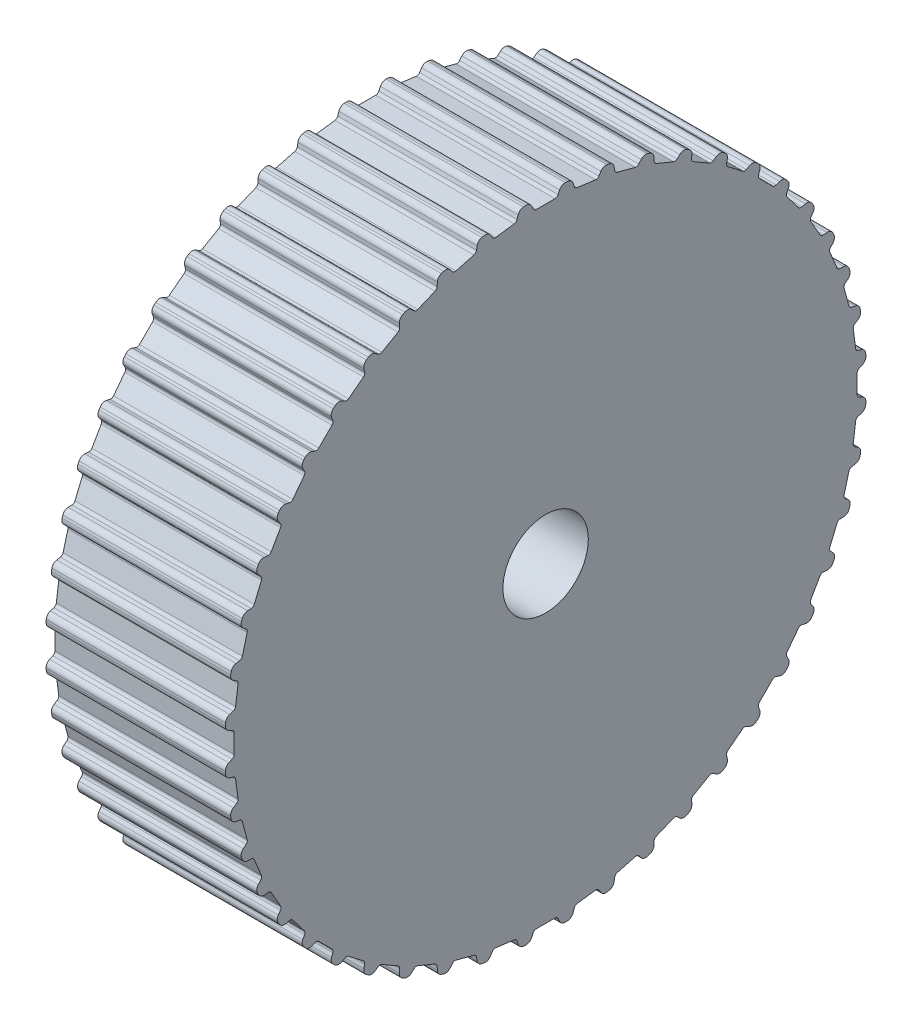
SolidWorks part; units mm, degrees
ref_plane "Front Plane" through (0, 0, 0) normal (0, 0, 1) x (1, 0, 0)
ref_plane "Top Plane" through (0, 0, 0) normal (0, 1, 0) x (1, 0, 0)
ref_plane "Right Plane" through (0, 0, 0) normal (1, 0, 0) x (0, 0, -1)
ref_plane "Plane1" through (0, 0, 0) normal (0, 0, -1) x (-1, 0, 0)
sketch "Sketch1" plane through (0, 0, 0) normal (0, 0, -1) x (-1, 0, 0)
  line L0 (-21, 37.585) -> (-21, 0)
  line L1 (-21, 0) -> (0, 0)
  line L2 (0, 0) -> (0, 37.585)
  line L3 (0, 37.585) -> (-21, 37.585)
  line L4 (-21, 0) -> (0, 0) construction
revolve "Revolve1" add sketch "Sketch1" angle 360 about L4 reverse direction yes
sketch "Sketch2" plane through (0, 0, 0) normal (-1, 0, 0) x (0, 0, 1)
  line L0 (3.0738, 37.4591) -> (3.4238, 36.3491)
  line L1 (3.4238, 36.3491) -> (6.1007, 35.9967)
  line L2 (6.1007, 35.9967) -> (6.7261, 36.9783)
  arc A0 (6.7261, 36.9783) -> (3.0738, 37.4591) centre (0, 0) ccw
extrude "Cut-Extrude1" cut sketch "Sketch2" against normal through all
sketch "Sketch3" plane through (0, 0, 0) normal (-1, 0, 0) x (0, 0, 1)
  line L0 (7.9369, 36.7374) -> (8.139, 35.5912)
  line L1 (8.139, 35.5912) -> (10.747, 34.8924)
  line L2 (10.747, 34.8924) -> (11.4951, 35.784)
  arc A0 (11.4951, 35.784) -> (7.9369, 36.7374) centre (0, 0) ccw
extrude "Cut-Extrude2" cut sketch "Sketch3" against normal through all
sketch "Sketch4" plane through (0, 0, 0) normal (-1, 0, 0) x (0, 0, 1)
  line L0 (12.6642, 35.3871) -> (12.715, 34.2244)
  line L1 (12.715, 34.2244) -> (15.2094, 33.1911)
  line L2 (15.2094, 33.1911) -> (16.0676, 33.9774)
  arc A0 (16.0676, 33.9774) -> (12.6642, 35.3871) centre (0, 0) ccw
extrude "Cut-Extrude3" cut sketch "Sketch4" against normal through all
sketch "Sketch5" plane through (0, 0, 0) normal (-1, 0, 0) x (0, 0, 1)
  line L0 (17.1748, 33.4314) -> (17.0734, 32.2719)
  line L1 (17.0734, 32.2719) -> (19.4116, 30.9219)
  line L2 (19.4116, 30.9219) -> (20.365, 31.5895)
  arc A0 (20.365, 31.5895) -> (17.1748, 33.4314) centre (0, 0) ccw
extrude "Cut-Extrude4" cut sketch "Sketch5" against normal through all
sketch "Sketch6" plane through (0, 0, 0) normal (-1, 0, 0) x (0, 0, 1)
  line L0 (21.3915, 30.9036) -> (21.1396, 29.7673)
  line L1 (21.1396, 29.7673) -> (23.2817, 28.1237)
  line L2 (23.2817, 28.1237) -> (24.3141, 28.6611)
  arc A0 (24.3141, 28.6611) -> (21.3915, 30.9036) centre (0, 0) ccw
extrude "Cut-Extrude5" cut sketch "Sketch6" against normal through all
sketch "Sketch7" plane through (0, 0, 0) normal (-1, 0, 0) x (0, 0, 1)
  line L0 (25.2423, 27.8471) -> (24.8442, 26.7534)
  line L1 (24.8442, 26.7534) -> (26.7534, 24.8442)
  line L2 (26.7534, 24.8442) -> (27.8471, 25.2423)
  arc A0 (27.8471, 25.2423) -> (25.2423, 27.8471) centre (0, 0) ccw
extrude "Cut-Extrude6" cut sketch "Sketch7" against normal through all
sketch "Sketch8" plane through (0, 0, 0) normal (-1, 0, 0) x (0, 0, 1)
  line L0 (28.6611, 24.3141) -> (28.1237, 23.2817)
  line L1 (28.1237, 23.2817) -> (29.7673, 21.1396)
  line L2 (29.7673, 21.1396) -> (30.9036, 21.3915)
  arc A0 (30.9036, 21.3915) -> (28.6611, 24.3141) centre (0, 0) ccw
extrude "Cut-Extrude7" cut sketch "Sketch8" against normal through all
sketch "Sketch9" plane through (0, 0, 0) normal (-1, 0, 0) x (0, 0, 1)
  line L0 (31.5895, 20.365) -> (30.9219, 19.4116)
  line L1 (30.9219, 19.4116) -> (32.2719, 17.0734)
  line L2 (32.2719, 17.0734) -> (33.4314, 17.1748)
  arc A0 (33.4314, 17.1748) -> (31.5895, 20.365) centre (0, 0) ccw
extrude "Cut-Extrude8" cut sketch "Sketch9" against normal through all
sketch "Sketch10" plane through (0, 0, 0) normal (-1, 0, 0) x (0, 0, 1)
  line L0 (33.9774, 16.0676) -> (33.1911, 15.2094)
  line L1 (33.1911, 15.2094) -> (34.2244, 12.715)
  line L2 (34.2244, 12.715) -> (35.3871, 12.6642)
  arc A0 (35.3871, 12.6642) -> (33.9774, 16.0676) centre (0, 0) ccw
extrude "Cut-Extrude9" cut sketch "Sketch10" against normal through all
sketch "Sketch11" plane through (0, 0, 0) normal (-1, 0, 0) x (0, 0, 1)
  line L0 (35.784, 11.4951) -> (34.8924, 10.747)
  line L1 (34.8924, 10.747) -> (35.5912, 8.139)
  line L2 (35.5912, 8.139) -> (36.7374, 7.9369)
  arc A0 (36.7374, 7.9369) -> (35.784, 11.4951) centre (0, 0) ccw
extrude "Cut-Extrude10" cut sketch "Sketch11" against normal through all
sketch "Sketch12" plane through (0, 0, 0) normal (-1, 0, 0) x (0, 0, 1)
  line L0 (36.9783, 6.7261) -> (35.9967, 6.1007)
  line L1 (35.9967, 6.1007) -> (36.3491, 3.4238)
  line L2 (36.3491, 3.4238) -> (37.4591, 3.0738)
  arc A0 (37.4591, 3.0738) -> (36.9783, 6.7261) centre (0, 0) ccw
extrude "Cut-Extrude11" cut sketch "Sketch12" against normal through all
sketch "Sketch13" plane through (0, 0, 0) normal (-1, 0, 0) x (0, 0, 1)
  line L0 (37.5398, 1.8419) -> (36.485, 1.35)
  line L1 (36.485, 1.35) -> (36.485, -1.35)
  line L2 (36.485, -1.35) -> (37.5398, -1.8419)
  arc A0 (37.5398, -1.8419) -> (37.5398, 1.8419) centre (0, 0) ccw
extrude "Cut-Extrude12" cut sketch "Sketch13" against normal through all
sketch "Sketch14" plane through (0, 0, 0) normal (-1, 0, 0) x (0, 0, 1)
  line L0 (37.4591, -3.0738) -> (36.3491, -3.4238)
  line L1 (36.3491, -3.4238) -> (35.9967, -6.1007)
  line L2 (35.9967, -6.1007) -> (36.9783, -6.7261)
  arc A0 (36.9783, -6.7261) -> (37.4591, -3.0738) centre (0, 0) ccw
extrude "Cut-Extrude13" cut sketch "Sketch14" against normal through all
sketch "Sketch15" plane through (0, 0, 0) normal (-1, 0, 0) x (0, 0, 1)
  line L0 (36.7374, -7.9369) -> (35.5912, -8.139)
  line L1 (35.5912, -8.139) -> (34.8924, -10.747)
  line L2 (34.8924, -10.747) -> (35.784, -11.4951)
  arc A0 (35.784, -11.4951) -> (36.7374, -7.9369) centre (0, 0) ccw
extrude "Cut-Extrude14" cut sketch "Sketch15" against normal through all
sketch "Sketch16" plane through (0, 0, 0) normal (-1, 0, 0) x (0, 0, 1)
  line L0 (35.3871, -12.6642) -> (34.2244, -12.715)
  line L1 (34.2244, -12.715) -> (33.1911, -15.2094)
  line L2 (33.1911, -15.2094) -> (33.9774, -16.0676)
  arc A0 (33.9774, -16.0676) -> (35.3871, -12.6642) centre (0, 0) ccw
extrude "Cut-Extrude15" cut sketch "Sketch16" against normal through all
sketch "Sketch17" plane through (0, 0, 0) normal (-1, 0, 0) x (0, 0, 1)
  line L0 (33.4314, -17.1748) -> (32.2719, -17.0734)
  line L1 (32.2719, -17.0734) -> (30.9219, -19.4116)
  line L2 (30.9219, -19.4116) -> (31.5895, -20.365)
  arc A0 (31.5895, -20.365) -> (33.4314, -17.1748) centre (0, 0) ccw
extrude "Cut-Extrude16" cut sketch "Sketch17" against normal through all
sketch "Sketch18" plane through (0, 0, 0) normal (-1, 0, 0) x (0, 0, 1)
  line L0 (30.9036, -21.3915) -> (29.7673, -21.1396)
  line L1 (29.7673, -21.1396) -> (28.1237, -23.2817)
  line L2 (28.1237, -23.2817) -> (28.6611, -24.3141)
  arc A0 (28.6611, -24.3141) -> (30.9036, -21.3915) centre (0, 0) ccw
extrude "Cut-Extrude17" cut sketch "Sketch18" against normal through all
sketch "Sketch19" plane through (0, 0, 0) normal (-1, 0, 0) x (0, 0, 1)
  line L0 (27.8471, -25.2423) -> (26.7534, -24.8442)
  line L1 (26.7534, -24.8442) -> (24.8442, -26.7534)
  line L2 (24.8442, -26.7534) -> (25.2423, -27.8471)
  arc A0 (25.2423, -27.8471) -> (27.8471, -25.2423) centre (0, 0) ccw
extrude "Cut-Extrude18" cut sketch "Sketch19" against normal through all
sketch "Sketch20" plane through (0, 0, 0) normal (-1, 0, 0) x (0, 0, 1)
  line L0 (24.3141, -28.6611) -> (23.2817, -28.1237)
  line L1 (23.2817, -28.1237) -> (21.1396, -29.7673)
  line L2 (21.1396, -29.7673) -> (21.3915, -30.9036)
  arc A0 (21.3915, -30.9036) -> (24.3141, -28.6611) centre (0, 0) ccw
extrude "Cut-Extrude19" cut sketch "Sketch20" against normal through all
sketch "Sketch21" plane through (0, 0, 0) normal (-1, 0, 0) x (0, 0, 1)
  line L0 (20.365, -31.5895) -> (19.4116, -30.9219)
  line L1 (19.4116, -30.9219) -> (17.0734, -32.2719)
  line L2 (17.0734, -32.2719) -> (17.1748, -33.4314)
  arc A0 (17.1748, -33.4314) -> (20.365, -31.5895) centre (0, 0) ccw
extrude "Cut-Extrude20" cut sketch "Sketch21" against normal through all
sketch "Sketch22" plane through (0, 0, 0) normal (-1, 0, 0) x (0, 0, 1)
  line L0 (16.0676, -33.9774) -> (15.2094, -33.1911)
  line L1 (15.2094, -33.1911) -> (12.715, -34.2244)
  line L2 (12.715, -34.2244) -> (12.6642, -35.3871)
  arc A0 (12.6642, -35.3871) -> (16.0676, -33.9774) centre (0, 0) ccw
extrude "Cut-Extrude21" cut sketch "Sketch22" against normal through all
sketch "Sketch23" plane through (0, 0, 0) normal (-1, 0, 0) x (0, 0, 1)
  line L0 (11.4951, -35.784) -> (10.747, -34.8924)
  line L1 (10.747, -34.8924) -> (8.139, -35.5912)
  line L2 (8.139, -35.5912) -> (7.9369, -36.7374)
  arc A0 (7.9369, -36.7374) -> (11.4951, -35.784) centre (0, 0) ccw
extrude "Cut-Extrude22" cut sketch "Sketch23" against normal through all
sketch "Sketch24" plane through (0, 0, 0) normal (-1, 0, 0) x (0, 0, 1)
  line L0 (6.7261, -36.9783) -> (6.1007, -35.9967)
  line L1 (6.1007, -35.9967) -> (3.4238, -36.3491)
  line L2 (3.4238, -36.3491) -> (3.0738, -37.4591)
  arc A0 (3.0738, -37.4591) -> (6.7261, -36.9783) centre (0, 0) ccw
extrude "Cut-Extrude23" cut sketch "Sketch24" against normal through all
sketch "Sketch25" plane through (0, 0, 0) normal (-1, 0, 0) x (0, 0, 1)
  line L0 (1.8419, -37.5398) -> (1.35, -36.485)
  line L1 (1.35, -36.485) -> (-1.35, -36.485)
  line L2 (-1.35, -36.485) -> (-1.8419, -37.5398)
  arc A0 (-1.8419, -37.5398) -> (1.8419, -37.5398) centre (0, 0) ccw
extrude "Cut-Extrude24" cut sketch "Sketch25" against normal through all
sketch "Sketch26" plane through (0, 0, 0) normal (-1, 0, 0) x (0, 0, 1)
  line L0 (-3.0738, -37.4591) -> (-3.4238, -36.3491)
  line L1 (-3.4238, -36.3491) -> (-6.1007, -35.9967)
  line L2 (-6.1007, -35.9967) -> (-6.7261, -36.9783)
  arc A0 (-6.7261, -36.9783) -> (-3.0738, -37.4591) centre (0, 0) ccw
extrude "Cut-Extrude25" cut sketch "Sketch26" against normal through all
sketch "Sketch27" plane through (0, 0, 0) normal (-1, 0, 0) x (0, 0, 1)
  line L0 (-7.9369, -36.7374) -> (-8.139, -35.5912)
  line L1 (-8.139, -35.5912) -> (-10.747, -34.8924)
  line L2 (-10.747, -34.8924) -> (-11.4951, -35.784)
  arc A0 (-11.4951, -35.784) -> (-7.9369, -36.7374) centre (0, 0) ccw
extrude "Cut-Extrude26" cut sketch "Sketch27" against normal through all
sketch "Sketch28" plane through (0, 0, 0) normal (-1, 0, 0) x (0, 0, 1)
  line L0 (-12.6642, -35.3871) -> (-12.715, -34.2244)
  line L1 (-12.715, -34.2244) -> (-15.2094, -33.1911)
  line L2 (-15.2094, -33.1911) -> (-16.0676, -33.9774)
  arc A0 (-16.0676, -33.9774) -> (-12.6642, -35.3871) centre (0, 0) ccw
extrude "Cut-Extrude27" cut sketch "Sketch28" against normal through all
sketch "Sketch29" plane through (0, 0, 0) normal (-1, 0, 0) x (0, 0, 1)
  line L0 (-17.1748, -33.4314) -> (-17.0734, -32.2719)
  line L1 (-17.0734, -32.2719) -> (-19.4116, -30.9219)
  line L2 (-19.4116, -30.9219) -> (-20.365, -31.5895)
  arc A0 (-20.365, -31.5895) -> (-17.1748, -33.4314) centre (0, 0) ccw
extrude "Cut-Extrude28" cut sketch "Sketch29" against normal through all
sketch "Sketch30" plane through (0, 0, 0) normal (-1, 0, 0) x (0, 0, 1)
  line L0 (-21.3915, -30.9036) -> (-21.1396, -29.7673)
  line L1 (-21.1396, -29.7673) -> (-23.2817, -28.1237)
  line L2 (-23.2817, -28.1237) -> (-24.3141, -28.6611)
  arc A0 (-24.3141, -28.6611) -> (-21.3915, -30.9036) centre (0, 0) ccw
extrude "Cut-Extrude29" cut sketch "Sketch30" against normal through all
sketch "Sketch31" plane through (0, 0, 0) normal (-1, 0, 0) x (0, 0, 1)
  line L0 (-25.2423, -27.8471) -> (-24.8442, -26.7534)
  line L1 (-24.8442, -26.7534) -> (-26.7534, -24.8442)
  line L2 (-26.7534, -24.8442) -> (-27.8471, -25.2423)
  arc A0 (-27.8471, -25.2423) -> (-25.2423, -27.8471) centre (0, 0) ccw
extrude "Cut-Extrude30" cut sketch "Sketch31" against normal through all
sketch "Sketch32" plane through (0, 0, 0) normal (-1, 0, 0) x (0, 0, 1)
  line L0 (-28.6611, -24.3141) -> (-28.1237, -23.2817)
  line L1 (-28.1237, -23.2817) -> (-29.7673, -21.1396)
  line L2 (-29.7673, -21.1396) -> (-30.9036, -21.3915)
  arc A0 (-30.9036, -21.3915) -> (-28.6611, -24.3141) centre (0, 0) ccw
extrude "Cut-Extrude31" cut sketch "Sketch32" against normal through all
sketch "Sketch33" plane through (0, 0, 0) normal (-1, 0, 0) x (0, 0, 1)
  line L0 (-31.5895, -20.365) -> (-30.9219, -19.4116)
  line L1 (-30.9219, -19.4116) -> (-32.2719, -17.0734)
  line L2 (-32.2719, -17.0734) -> (-33.4314, -17.1748)
  arc A0 (-33.4314, -17.1748) -> (-31.5895, -20.365) centre (0, 0) ccw
extrude "Cut-Extrude32" cut sketch "Sketch33" against normal through all
sketch "Sketch34" plane through (0, 0, 0) normal (-1, 0, 0) x (0, 0, 1)
  line L0 (-33.9774, -16.0676) -> (-33.1911, -15.2094)
  line L1 (-33.1911, -15.2094) -> (-34.2244, -12.715)
  line L2 (-34.2244, -12.715) -> (-35.3871, -12.6642)
  arc A0 (-35.3871, -12.6642) -> (-33.9774, -16.0676) centre (0, 0) ccw
extrude "Cut-Extrude33" cut sketch "Sketch34" against normal through all
sketch "Sketch35" plane through (0, 0, 0) normal (-1, 0, 0) x (0, 0, 1)
  line L0 (-35.784, -11.4951) -> (-34.8924, -10.747)
  line L1 (-34.8924, -10.747) -> (-35.5912, -8.139)
  line L2 (-35.5912, -8.139) -> (-36.7374, -7.9369)
  arc A0 (-36.7374, -7.9369) -> (-35.784, -11.4951) centre (0, 0) ccw
extrude "Cut-Extrude34" cut sketch "Sketch35" against normal through all
sketch "Sketch36" plane through (0, 0, 0) normal (-1, 0, 0) x (0, 0, 1)
  line L0 (-36.9783, -6.7261) -> (-35.9967, -6.1007)
  line L1 (-35.9967, -6.1007) -> (-36.3491, -3.4238)
  line L2 (-36.3491, -3.4238) -> (-37.4591, -3.0738)
  arc A0 (-37.4591, -3.0738) -> (-36.9783, -6.7261) centre (0, 0) ccw
extrude "Cut-Extrude35" cut sketch "Sketch36" against normal through all
sketch "Sketch37" plane through (0, 0, 0) normal (-1, 0, 0) x (0, 0, 1)
  line L0 (-37.5398, -1.8419) -> (-36.485, -1.35)
  line L1 (-36.485, -1.35) -> (-36.485, 1.35)
  line L2 (-36.485, 1.35) -> (-37.5398, 1.8419)
  arc A0 (-37.5398, 1.8419) -> (-37.5398, -1.8419) centre (0, 0) ccw
extrude "Cut-Extrude36" cut sketch "Sketch37" against normal through all
sketch "Sketch38" plane through (0, 0, 0) normal (-1, 0, 0) x (0, 0, 1)
  line L0 (-37.4591, 3.0738) -> (-36.3491, 3.4238)
  line L1 (-36.3491, 3.4238) -> (-35.9967, 6.1007)
  line L2 (-35.9967, 6.1007) -> (-36.9783, 6.7261)
  arc A0 (-36.9783, 6.7261) -> (-37.4591, 3.0738) centre (0, 0) ccw
extrude "Cut-Extrude37" cut sketch "Sketch38" against normal through all
sketch "Sketch39" plane through (0, 0, 0) normal (-1, 0, 0) x (0, 0, 1)
  line L0 (-36.7374, 7.9369) -> (-35.5912, 8.139)
  line L1 (-35.5912, 8.139) -> (-34.8924, 10.747)
  line L2 (-34.8924, 10.747) -> (-35.784, 11.4951)
  arc A0 (-35.784, 11.4951) -> (-36.7374, 7.9369) centre (0, 0) ccw
extrude "Cut-Extrude38" cut sketch "Sketch39" against normal through all
sketch "Sketch40" plane through (0, 0, 0) normal (-1, 0, 0) x (0, 0, 1)
  line L0 (-35.3871, 12.6642) -> (-34.2244, 12.715)
  line L1 (-34.2244, 12.715) -> (-33.1911, 15.2094)
  line L2 (-33.1911, 15.2094) -> (-33.9774, 16.0676)
  arc A0 (-33.9774, 16.0676) -> (-35.3871, 12.6642) centre (0, 0) ccw
extrude "Cut-Extrude39" cut sketch "Sketch40" against normal through all
sketch "Sketch41" plane through (0, 0, 0) normal (-1, 0, 0) x (0, 0, 1)
  line L0 (-33.4314, 17.1748) -> (-32.2719, 17.0734)
  line L1 (-32.2719, 17.0734) -> (-30.9219, 19.4116)
  line L2 (-30.9219, 19.4116) -> (-31.5895, 20.365)
  arc A0 (-31.5895, 20.365) -> (-33.4314, 17.1748) centre (0, 0) ccw
extrude "Cut-Extrude40" cut sketch "Sketch41" against normal through all
sketch "Sketch42" plane through (0, 0, 0) normal (-1, 0, 0) x (0, 0, 1)
  line L0 (-30.9036, 21.3915) -> (-29.7673, 21.1396)
  line L1 (-29.7673, 21.1396) -> (-28.1237, 23.2817)
  line L2 (-28.1237, 23.2817) -> (-28.6611, 24.3141)
  arc A0 (-28.6611, 24.3141) -> (-30.9036, 21.3915) centre (0, 0) ccw
extrude "Cut-Extrude41" cut sketch "Sketch42" against normal through all
sketch "Sketch43" plane through (0, 0, 0) normal (-1, 0, 0) x (0, 0, 1)
  line L0 (-27.8471, 25.2423) -> (-26.7534, 24.8442)
  line L1 (-26.7534, 24.8442) -> (-24.8442, 26.7534)
  line L2 (-24.8442, 26.7534) -> (-25.2423, 27.8471)
  arc A0 (-25.2423, 27.8471) -> (-27.8471, 25.2423) centre (0, 0) ccw
extrude "Cut-Extrude42" cut sketch "Sketch43" against normal through all
sketch "Sketch44" plane through (0, 0, 0) normal (-1, 0, 0) x (0, 0, 1)
  line L0 (-24.3141, 28.6611) -> (-23.2817, 28.1237)
  line L1 (-23.2817, 28.1237) -> (-21.1396, 29.7673)
  line L2 (-21.1396, 29.7673) -> (-21.3915, 30.9036)
  arc A0 (-21.3915, 30.9036) -> (-24.3141, 28.6611) centre (0, 0) ccw
extrude "Cut-Extrude43" cut sketch "Sketch44" against normal through all
sketch "Sketch45" plane through (0, 0, 0) normal (-1, 0, 0) x (0, 0, 1)
  line L0 (-20.365, 31.5895) -> (-19.4116, 30.9219)
  line L1 (-19.4116, 30.9219) -> (-17.0734, 32.2719)
  line L2 (-17.0734, 32.2719) -> (-17.1748, 33.4314)
  arc A0 (-17.1748, 33.4314) -> (-20.365, 31.5895) centre (0, 0) ccw
extrude "Cut-Extrude44" cut sketch "Sketch45" against normal through all
sketch "Sketch46" plane through (0, 0, 0) normal (-1, 0, 0) x (0, 0, 1)
  line L0 (-16.0676, 33.9774) -> (-15.2094, 33.1911)
  line L1 (-15.2094, 33.1911) -> (-12.715, 34.2244)
  line L2 (-12.715, 34.2244) -> (-12.6642, 35.3871)
  arc A0 (-12.6642, 35.3871) -> (-16.0676, 33.9774) centre (0, 0) ccw
extrude "Cut-Extrude45" cut sketch "Sketch46" against normal through all
sketch "Sketch47" plane through (0, 0, 0) normal (-1, 0, 0) x (0, 0, 1)
  line L0 (-11.4951, 35.784) -> (-10.747, 34.8924)
  line L1 (-10.747, 34.8924) -> (-8.139, 35.5912)
  line L2 (-8.139, 35.5912) -> (-7.9369, 36.7374)
  arc A0 (-7.9369, 36.7374) -> (-11.4951, 35.784) centre (0, 0) ccw
extrude "Cut-Extrude46" cut sketch "Sketch47" against normal through all
sketch "Sketch48" plane through (0, 0, 0) normal (-1, 0, 0) x (0, 0, 1)
  line L0 (-6.7261, 36.9783) -> (-6.1007, 35.9967)
  line L1 (-6.1007, 35.9967) -> (-3.4238, 36.3491)
  line L2 (-3.4238, 36.3491) -> (-3.0738, 37.4591)
  arc A0 (-3.0738, 37.4591) -> (-6.7261, 36.9783) centre (0, 0) ccw
extrude "Cut-Extrude47" cut sketch "Sketch48" against normal through all
sketch "Sketch49" plane through (0, 0, 0) normal (-1, 0, 0) x (0, 0, 1)
  line L0 (-1.8419, 37.5398) -> (-1.35, 36.485)
  line L1 (-1.35, 36.485) -> (1.35, 36.485)
  line L2 (1.35, 36.485) -> (1.8419, 37.5398)
  arc A0 (1.8419, 37.5398) -> (-1.8419, 37.5398) centre (0, 0) ccw
extrude "Cut-Extrude48" cut sketch "Sketch49" against normal through all
sketch "Sketch50" plane through (0, 0, 0) normal (0, 0, -1) x (-1, 0, 0)
  line L0 (-27, 25) -> (-27, 0)
  line L1 (-27, 0) -> (-21, 0)
  line L2 (-21, 0) -> (-21, 25)
  line L3 (-21, 25) -> (-27, 25)
  line L4 (-27, 0) -> (-21, 0) construction
revolve "Revolve2" add sketch "Sketch50" angle 360 about L4 reverse direction yes
hole_wizard "Ø8.0 (8) Diameter Hole1" positions "Sketch52" profile "Sketch51" hole size "Ø8.0" standard "ANSI Metric"
sketch "Sketch52" plane through (27, 0, 0) normal (1, 0, 0) x (0, 0, -1)
  point P0 (0, 0)
sketch "Sketch51" plane through (27, 0, 0) normal (0, 1, 0) x (0, 0, -1)
  line L0 (0, 0) -> (0, 27)
  line L1 (0, 27) -> (4, 27)
  line L2 (4, 27) -> (4, 0)
  line L5 (4, 0) -> (0, 0)
  line L11 (0, -6.35) -> (0, 107.95) construction
  dimension "Thru Hole Dia." = 8
  dimension "Thru Hole Depth" = 27
fillet "Fillet1" radius 0.4 96 edges at (10.5, -19.4116, -30.9219) (10.5, 36.485, -1.35) (10.5, 17.0734, -32.2719) (10.5, 36.3491, 3.4238) (10.5, -32.2719, -17.0734) (10.5, 34.8924, 10.747) (10.5, -1.35, -36.485) (10.5, 35.5912, 8.139) (10.5, 30.9219, -19.4116) (10.5, 33.1911, 15.2094) (10.5, -35.5912, -8.139) (10.5, 34.2244, 12.715) (10.5, -26.7534, -24.8442) (10.5, 30.9219, 19.4116) (10.5, -10.747, -34.8924) (10.5, 32.2719, 17.0734) (10.5, 8.139, -35.5912) (10.5, 28.1237, 23.2817) (10.5, 24.8442, -26.7534) (10.5, 29.7673, 21.1396) (10.5, 34.8924, -10.747) (10.5, 24.8442, 26.7534) (10.5, -36.3491, -3.4238) (10.5, 26.7534, 24.8442) (10.5, -34.2244, -12.715) (10.5, 21.1396, 29.7673) (10.5, -29.7673, -21.1396) (10.5, 23.2817, 28.1237) (10.5, -23.2817, -28.1237) (10.5, 17.0734, 32.2719) (10.5, -15.2094, -33.1911) (10.5, 19.4116, 30.9219) (10.5, -6.1007, -35.9967) (10.5, 12.715, 34.2244) (10.5, 3.4238, -36.3491) (10.5, 15.2094, 33.1911) (10.5, 12.715, -34.2244) (10.5, 8.139, 35.5912) (10.5, 21.1396, -29.7673) (10.5, 10.747, 34.8924) (10.5, 28.1237, -23.2817) (10.5, 3.4238, 36.3491) (10.5, 33.1911, -15.2094) (10.5, 6.1007, 35.9967) (10.5, 35.9967, -6.1007) (10.5, -1.35, 36.485) (10.5, -35.9967, -6.1007) (10.5, 1.35, 36.485) (10.5, -34.8924, -10.747) (10.5, -6.1007, 35.9967) (10.5, -33.1911, -15.2094) (10.5, -3.4238, 36.3491) (10.5, -30.9219, -19.4116) (10.5, -10.747, 34.8924) (10.5, -28.1237, -23.2817) (10.5, -8.139, 35.5912) (10.5, -24.8442, -26.7534) (10.5, -15.2094, 33.1911) (10.5, -21.1396, -29.7673) (10.5, -12.715, 34.2244) (10.5, -17.0734, -32.2719) (10.5, -19.4116, 30.9219) (10.5, -12.715, -34.2244) (10.5, -17.0734, 32.2719) (10.5, -8.139, -35.5912) (10.5, -23.2817, 28.1237) (10.5, -3.4238, -36.3491) (10.5, -21.1396, 29.7673) (10.5, 1.35, -36.485) (10.5, -26.7534, 24.8442) (10.5, 6.1007, -35.9967) (10.5, -24.8442, 26.7534) (10.5, 10.747, -34.8924) (10.5, -29.7673, 21.1396) (10.5, 15.2094, -33.1911) (10.5, -28.1237, 23.2817) (10.5, 19.4116, -30.9219) (10.5, -32.2719, 17.0734) (10.5, 23.2817, -28.1237) (10.5, -30.9219, 19.4116) (10.5, 26.7534, -24.8442) (10.5, -34.2244, 12.715) (10.5, 29.7673, -21.1396) (10.5, -33.1911, 15.2094) (10.5, 32.2719, -17.0734) (10.5, -35.5912, 8.139) (10.5, 34.2244, -12.715) (10.5, -34.8924, 10.747) (10.5, 35.5912, -8.139) (10.5, -36.3491, 3.4238) (10.5, 36.3491, -3.4238) (10.5, -35.9967, 6.1007) (10.5, 36.485, 1.35) (10.5, -36.485, -1.35) (10.5, 35.9967, 6.1007) (10.5, -36.485, 1.35) tangent propagation no
fillet "Fillet2" radius 0.7 96 edges at (10.5, -20.365, -31.5895) (10.5, 36.9783, 6.7261) (10.5, 17.1748, -33.4314) (10.5, 37.4591, 3.0738) (10.5, -33.4314, -17.1748) (10.5, 35.784, 11.4951) (10.5, -1.8419, -37.5398) (10.5, 36.7374, 7.9369) (10.5, 31.5895, -20.365) (10.5, 33.9774, 16.0676) (10.5, -36.7374, -7.9369) (10.5, 35.3871, 12.6642) (10.5, -27.8471, -25.2423) (10.5, 31.5895, 20.365) (10.5, -11.4951, -35.784) (10.5, 33.4314, 17.1748) (10.5, 7.9369, -36.7374) (10.5, 28.6611, 24.3141) (10.5, 25.2423, -27.8471) (10.5, 30.9036, 21.3915) (10.5, 35.784, -11.4951) (10.5, 25.2423, 27.8471) (10.5, -37.4591, -3.0738) (10.5, 27.8471, 25.2423) (10.5, -35.3871, -12.6642) (10.5, 21.3915, 30.9036) (10.5, -30.9036, -21.3915) (10.5, 24.3141, 28.6611) (10.5, -24.3141, -28.6611) (10.5, 17.1748, 33.4314) (10.5, -16.0676, -33.9774) (10.5, 20.365, 31.5895) (10.5, -6.7261, -36.9783) (10.5, 12.6642, 35.3871) (10.5, 3.0738, -37.4591) (10.5, 16.0676, 33.9774) (10.5, 12.6642, -35.3871) (10.5, 7.9369, 36.7374) (10.5, 21.3915, -30.9036) (10.5, 11.4951, 35.784) (10.5, 28.6611, -24.3141) (10.5, 3.0738, 37.4591) (10.5, 33.9774, -16.0676) (10.5, 6.7261, 36.9783) (10.5, 36.9783, -6.7261) (10.5, -1.8419, 37.5398) (10.5, -36.9783, -6.7261) (10.5, 1.8419, 37.5398) (10.5, -35.784, -11.4951) (10.5, -6.7261, 36.9783) (10.5, -33.9774, -16.0676) (10.5, -3.0738, 37.4591) (10.5, -31.5895, -20.365) (10.5, -11.4951, 35.784) (10.5, -28.6611, -24.3141) (10.5, -7.9369, 36.7374) (10.5, -25.2423, -27.8471) (10.5, -16.0676, 33.9774) (10.5, -21.3915, -30.9036) (10.5, -12.6642, 35.3871) (10.5, -17.1748, -33.4314) (10.5, -20.365, 31.5895) (10.5, -12.6642, -35.3871) (10.5, -17.1748, 33.4314) (10.5, -7.9369, -36.7374) (10.5, -24.3141, 28.6611) (10.5, -3.0738, -37.4591) (10.5, -21.3915, 30.9036) (10.5, 1.8419, -37.5398) (10.5, -27.8471, 25.2423) (10.5, 6.7261, -36.9783) (10.5, -25.2423, 27.8471) (10.5, 11.4951, -35.784) (10.5, -30.9036, 21.3915) (10.5, 16.0676, -33.9774) (10.5, -28.6611, 24.3141) (10.5, 20.365, -31.5895) (10.5, -33.4314, 17.1748) (10.5, 24.3141, -28.6611) (10.5, -31.5895, 20.365) (10.5, 27.8471, -25.2423) (10.5, -35.3871, 12.6642) (10.5, 30.9036, -21.3915) (10.5, -33.9774, 16.0676) (10.5, 33.4314, -17.1748) (10.5, -36.7374, 7.9369) (10.5, 35.3871, -12.6642) (10.5, -35.784, 11.4951) (10.5, 36.7374, -7.9369) (10.5, -37.4591, 3.0738) (10.5, 37.4591, -3.0738) (10.5, -36.9783, 6.7261) (10.5, 37.5398, 1.8419) (10.5, -37.5398, -1.8419) (10.5, -37.5398, 1.8419) (10.5, 37.5398, -1.8419) tangent propagation no
sketch "Sketch53" plane through (27, 0, 0) normal (1, 0, 0) x (0, 0, -1)
  circle A0 centre (0, 0) radius 5
  dimension "D1" = 10
extrude "Cut-Extrude49" cut sketch "Sketch53" against normal through all
sketch "Sketch54" plane through (27, 0, 0) normal (1, 0, 0) x (0, 0, -1)
  circle A1 centre (0, 0) radius 25
  circle A2 centre (0, 0) radius 25
  dimension "D1" = 0
extrude "Cut-Extrude50" cut sketch "Sketch54" against normal up to surface (6 mm away) up to face at (21, 0, -25)
ref_plane "Plane2" through (0, -37.585, 0) normal (0, -1, 0) x (-1, 0, 0)
ref_axis "Axis1" through (0, 0, 0) along (1, 0, 0)
sketch "Sketch55" plane through (0, -37.585, 0) normal (0, -1, 0) x (-1, 0, 0)
  line L0 (0, 0) -> (-21, 0) construction
  line L1 (-21, -1.0952) -> (-21, 1.0952) construction
  circle A0 centre (-10.5, 0) radius 4.5
  point P2 (0, 0)
  point P3 (0, 0)
  point P4 (0, 0)
  point P7 (-7.2543, 0)
  dimension "D1" = 9
  dimension "D2" = 10.5
extrude "Cut-Extrude51" cut sketch "Sketch55" against normal blind 17.59
sketch "Sketch56" plane through (0, -19.995, 0) normal (0, -1, 0) x (1, 0, 0)
  point P0 (10.5, 0)
  point P1 (0, 0)
hole_wizard "Tap Drill for M5 Tap1" positions "3DSketch1" profile "Sketch57" hole size "M5" standard "DIN" end condition up to next
sketch3d "3DSketch1"
  point P0 (10.5, -19.995, 0)
sketch "Sketch57" plane through (10.5, -19.995, 0) normal (1, 0, 0) x (0, 0, -1)
  line L0 (0, 0) -> (0, 14.995)
  line L1 (0, 14.995) -> (2.1, 14.995)
  line L2 (2.1, 14.995) -> (2.1, 0)
  line L5 (2.1, 0) -> (0, 0)
  line L11 (0, -6.35) -> (0, 107.95) construction
  dimension "Thru Hole Dia." = 4.2
  dimension "Thru Hole Depth" = 14.995
